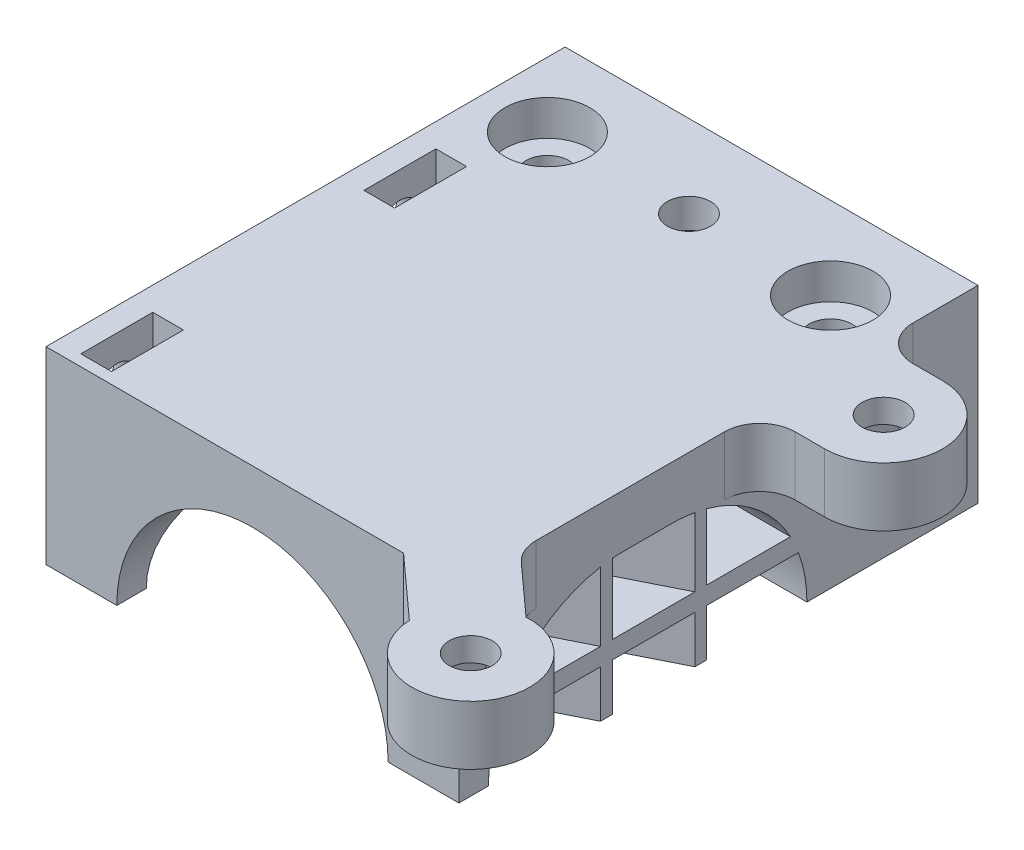
SolidWorks part; units mm, degrees
ref_plane "Front Plane" through (0, 0, 0) normal (0, 0, 1) x (1, 0, 0)
ref_plane "Top Plane" through (0, 0, 0) normal (0, 1, 0) x (1, 0, 0)
ref_plane "Right Plane" through (0, 0, 0) normal (1, 0, 0) x (0, 0, -1)
sketch "Sketch12" plane through (0, 0, 0) normal (0, -1, 0) x (-1, 0, 0)
  line L0 (3.5, -33.75) -> (3.5, -22) construction
  line L4 (21, -21) -> (-14, -21)
  line L5 (21, -21) -> (21, -65)
  line L6 (21, -65) -> (-14, -65)
  line L7 (-14, -21) -> (-14, -65)
  dimension "D1" = 35
  dimension "D2" = 44
extrude "chamber" add sketch "Sketch12" against normal blind 16 separate body
sketch "Sketch13" plane through (0, 0, 65) normal (0, 0, 1) x (1, 0, 0)
  line L1 (-21, 0) -> (-21, 16) construction
  line L5 (14, 16) -> (-21, 16) construction
  circle A0 centre (-3.5, 16) radius 11.5
  dimension "D3" = 23
  dimension "D2" = 17.5
extrude "body" cut sketch "Sketch13" against normal blind 31
sketch "Sketch14" plane through (14, 0, 0) normal (1, 0, 0) x (0, 0, -1)
  line L0 (-51, 16) -> (-47, 16) construction
  line L2 (-65, 16) -> (-65, 0) construction
  line L3 (-51, 27.5) -> (-47, 27.5)
  line L4 (-51, 4.5) -> (-47, 4.5)
  line L6 (-21, 16) -> (-65, 16) construction
  arc A0 (-51, 27.5) -> (-51, 4.5) centre (-51, 16) ccw
  arc A1 (-47, 4.5) -> (-47, 27.5) centre (-47, 16) ccw
  point P6 (-49, 16)
  dimension "D3" = 11.5
  dimension "D1" = 16
  dimension "D4" = 4
extrude "hot-end-tonel" cut sketch "Sketch14" against normal through all
sketch "Sketch26" plane through (14, 0, 0) normal (1, 0, 0) x (0, 0, -1)
  line L1 (-62.5, 12) -> (-35.5, 12)
  line L2 (-62.5, 12) -> (-62.5, 10.5)
  line L3 (-62.5, 10.5) -> (-35.5, 10.5)
  line L4 (-35.5, 12) -> (-35.5, 10.5)
  line L6 (-21, 16) -> (-35.5, 16) construction
  dimension "D1" = 1.5
  dimension "D2" = 4
extrude "grid-v" add sketch "Sketch26" against normal blind 6
sketch "Sketch27" plane through (0, 0, 0) normal (0, -1, 0) x (1, 0, 0)
  line L0 (8, 56) -> (14, 53)
  line L1 (14, 21) -> (14, 65) construction
  line L2 (14, 53) -> (14, 52)
  line L3 (14, 52) -> (8, 55)
  line L4 (8, 55) -> (8, 56)
  line L5 (14, 44) -> (8, 47)
  line L6 (8, 47) -> (8, 48)
  line L7 (8, 48) -> (14, 45)
  line L8 (14, 45) -> (14, 44)
  line L9 (14, 65) -> (-21, 65) construction
  dimension "D1" = 6
  dimension "D2" = 1
  dimension "D4" = 12
  dimension "D5" = 9
  dimension "D6" = 8
  dimension "D3" = 2
extrude "grid-h" add sketch "Sketch27" against normal blind 16
sketch "Sketch16" plane through (-21, 0, 0) normal (1, 0, 0) x (0, 0, -1)
  line L3 (-21, 16) -> (-35.5, 16) construction
  line L4 (-51, 4.5) -> (-47, 4.5) construction
  circle A0 centre (-49, 16) radius 13.5
  point P12 (-49, 4.5)
ref_plane "Plane2" through (-17, 0, 0) normal (-1, 0, 0) x (0, 0, 1)
sketch "Sketch18" plane through (-17, 0, 0) normal (-1, 0, 0) x (0, 0, 1)
  circle A0 centre (49, 16) radius 11.5
  circle A1 centre (49, 16) radius 13.5 construction
  dimension "D1" = 2
loft "Cut-Loft1" cut profiles "Sketch16", "Sketch18" connector at (-21, 9.106, 37.393) connector at (-17, 8.5149, 40.2694)
sketch "Sketch20" plane through (0, 0, 34) normal (0, 0, 1) x (1, 0, 0)
  circle A0 centre (-3.5, 16) radius 8.125
  dimension "D1" = 16.25
extrude "hot-end-1" cut sketch "Sketch20" against normal blind 3.2
sketch "Sketch21" plane through (0, 0, 30.8) normal (0, 0, 1) x (1, 0, 0)
  circle A0 centre (-3.5, 16) radius 7
  dimension "D1" = 14
extrude "hot-end-2" cut sketch "Sketch21" against normal blind 5.6
sketch "Sketch22" plane through (0, 0, 25.2) normal (0, 0, 1) x (1, 0, 0)
  circle A0 centre (-3.5, 16) radius 8.125
extrude "hot-end-3" cut sketch "Sketch22" against normal blind 4.2
sketch "Sketch24" plane through (0, 0, 0) normal (0, -1, 0) x (1, 0, 0)
  line L0 (14, 21) -> (14, 65) construction
  line L1 (-21, 21) -> (14, 21) construction
  circle A0 centre (-15.5, 28) radius 1.825
  circle A1 centre (8.5, 28) radius 1.825
  dimension "D3" = 3.65
  dimension "D1" = 24
  dimension "D2" = 5.5
  dimension "D4" = 7
extrude "mount-holes" cut sketch "Sketch24" against normal through all
sketch "Sketch25" plane through (-21, 0, 0) normal (-1, 0, 0) x (0, 0, 1)
  line L0 (35.5, 16) -> (21, 16) construction
  line L1 (35.5, 16) -> (62.5, 15.9969) construction
  circle A0 centre (61, 4) radius 1.75
  circle A1 centre (37, 4) radius 1.75
  point P6 (49, 15.9985)
  dimension "D1" = 3.5
  dimension "D3" = 24
  dimension "D4" = 12
  dimension "D5" = 12
extrude "fan-mount-holes" cut sketch "Sketch25" against normal blind 8
sketch "Sketch34" plane through (-21, 0, 0) normal (-1, 0, 0) x (0, 0, 1)
  line L0 (33.95, 0) -> (40.05, 0)
  line L1 (37, 0.4782) -> (40.8, 2.6721) construction
  line L2 (40.05, 0) -> (40.05, 5.7609)
  line L3 (40.05, 5.7609) -> (37, 7.5218)
  line L4 (37, 7.5218) -> (33.95, 5.7609)
  line L5 (33.95, 5.7609) -> (33.95, 0)
  line L6 (34.7, 1.8061) -> (37, 0.4782) construction
  line L7 (61, 0.4782) -> (64.8, 2.6721) construction
  line L8 (64.05, 0) -> (64.05, 5.7609)
  line L9 (64.05, 5.7609) -> (61, 7.5218)
  line L10 (61, 7.5218) -> (57.95, 5.7609)
  line L11 (57.95, 5.7609) -> (57.95, 0)
  line L12 (58.7, 1.8061) -> (61, 0.4782) construction
  line L13 (65, 0) -> (21, 0) construction
  line L14 (57.95, 0) -> (64.05, 0)
  circle A0 centre (37, 4) radius 3.05 construction
  circle A1 centre (61, 4) radius 3.05 construction
  dimension "D1" = 6.1
extrude "fan-mount-nut-holes" cut sketch "Sketch34" against normal blind 2.6 from offset 2 offset against normal yes
mirror "Mirror1" about plane through (0, 16, 0) normal (0, 1, 0) of bodies 143 133
delete or keep bodies "Body-Delete/Keep 1" type delete bodies bodies 143
sketch "Sketch29" [suppressed] plane through (0, 16, 0) normal (0, 1, 0) x (1, 0, 0)
  line L0 (-21, -24.95) -> (-21, -31.05)
  line L1 (-11.9782, -28) -> (-13.7391, -24.95)
  line L2 (-13.7391, -24.95) -> (-21, -24.95)
  line L3 (-17.2609, -24.95) -> (-19.0218, -28) construction
  line L4 (-19.0218, -28) -> (-17.2609, -31.05) construction
  line L5 (-21, -31.05) -> (-13.7391, -31.05)
  line L6 (-13.7391, -31.05) -> (-11.9782, -28)
  line L7 (4.9782, -28) -> (6.7391, -31.05)
  line L8 (6.7391, -31.05) -> (14, -31.05)
  line L9 (10.2609, -31.05) -> (12.0218, -28) construction
  line L10 (12.0218, -28) -> (10.2609, -24.95) construction
  line L11 (14, -24.95) -> (6.7391, -24.95)
  line L12 (6.7391, -24.95) -> (4.9782, -28)
  line L13 (-21, -35.5) -> (-21, -21) construction
  line L14 (14, -24.95) -> (14, -31.05)
  line L15 (14, -21) -> (14, -35.5) construction
  circle A0 centre (-15.5, -28) radius 3.05 construction
  circle A1 centre (8.5, -28) radius 3.05 construction
  dimension "D1" = 6.1
extrude "Cut-Extrude4" [suppressed] cut sketch "Sketch29" against normal blind 2.6 from offset 3 offset against normal yes
pattern_linear "LPattern1" [suppressed] count 2 spacing 5.7 of bodies 138
sketch "Sketch32" plane through (0, 32, 0) normal (0, -1, 0) x (-1, 0, 0)
  line L1 (21, -21) -> (-14, -21) construction
  circle A0 centre (3.5, -28) radius 1.825
  point P5 (3.5, -21)
  dimension "D1" = 3.65
  dimension "D2" = 7
extrude "hot-end-screw-hole" cut sketch "Sketch32" along normal blind 20 contours A0
sketch "Sketch33" plane through (0, 32, 0) normal (0, -1, 0) x (1, 0, 0)
  line L0 (-6.55, 21) -> (-0.45, 21)
  line L1 (-3.5, 24.4782) -> (-0.45, 26.2391) construction
  line L2 (-0.45, 21) -> (-0.45, 29.7609)
  line L3 (-0.45, 29.7609) -> (-3.5, 31.5218)
  line L4 (-3.5, 31.5218) -> (-6.55, 29.7609)
  line L5 (-6.55, 29.7609) -> (-6.55, 21)
  line L6 (-6.55, 26.2391) -> (-3.5, 24.4782) construction
  line L8 (-21, 21) -> (14, 21) construction
  circle A0 centre (-3.5, 28) radius 3.05 construction
  dimension "D1" = 6.1
extrude "hot-end-nut-hole" cut sketch "Sketch33" along normal blind 2.6 from offset 2.5
sketch "Sketch35" plane through (0, 32, 0) normal (0, 1, 0) x (1, 0, 0)
  line L1 (14, -21) -> (14, -65) construction
  line L2 (9.3051, -65) -> (14.504, -69.7012)
  line L4 (14, -65) -> (-21, -65) construction
  line L5 (14, -39.5) -> (14, -29.5)
  line L6 (19.199, -64.5091) -> (14, -59.8079)
  line L7 (14, -39.5) -> (19.5, -39.5)
  line L8 (19.5, -29.5) -> (14, -29.5)
  line L10 (14, -59.8079) -> (9.3051, -65)
  circle A0 centre (19.5, -69.5) radius 1.825
  arc A1 (19.5, -39.5) -> (19.5, -29.5) centre (19.5, -34.5) ccw
  arc A2 (14.504, -69.7012) -> (19.199, -64.5091) centre (19.5, -69.5) ccw
  circle A3 centre (19.5, -34.5) radius 1.825
  dimension "D1" = 3.65
  dimension "D2" = 5
  dimension "D3" = 35
  dimension "D4" = 5.5
  dimension "D5" = 4.5
  dimension "D6" = 7
extrude "Boss-Extrude1" add sketch "Sketch35" against normal blind 5
sketch "Sketch36" plane through (0, 27, 0) normal (0, -1, 0) x (1, 0, 0)
  line L7 (17.7391, 31.45) -> (21.2609, 31.45)
  line L8 (21.2609, 31.45) -> (23.0218, 34.5)
  line L9 (23.0218, 34.5) -> (21.2609, 37.55)
  line L10 (21.2609, 37.55) -> (17.7391, 37.55)
  line L11 (17.7391, 37.55) -> (15.9782, 34.5)
  line L12 (15.9782, 34.5) -> (17.7391, 31.45)
  line L13 (23.0218, 69.5) -> (21.2609, 72.55)
  line L14 (21.2609, 72.55) -> (17.7391, 72.55)
  line L15 (17.7391, 72.55) -> (15.9782, 69.5)
  line L16 (15.9782, 69.5) -> (17.7391, 66.45)
  line L17 (17.7391, 66.45) -> (21.2609, 66.45)
  line L18 (21.2609, 66.45) -> (23.0218, 69.5)
  circle A1 centre (19.5, 34.5) radius 3.05 construction
  circle A2 centre (19.5, 69.5) radius 3.05 construction
  dimension "D2" = 6.1
extrude "Cut-Extrude5" cut sketch "Sketch36" against normal blind 3
sketch "Sketch37" plane through (0, 32, 0) normal (0, 1, 0) x (1, 0, 0)
  circle A0 centre (-15.5, -28) radius 3.6
  circle A1 centre (8.5, -28) radius 3.6
  dimension "D1" = 7.2
extrude "Cut-Extrude6" cut sketch "Sketch37" against normal blind 3
fillet "Fillet1" radius 3 3 edges at (14, 29.5, 59.8079) (14, 29.5, 29.5) (14, 29.5, 39.5)
